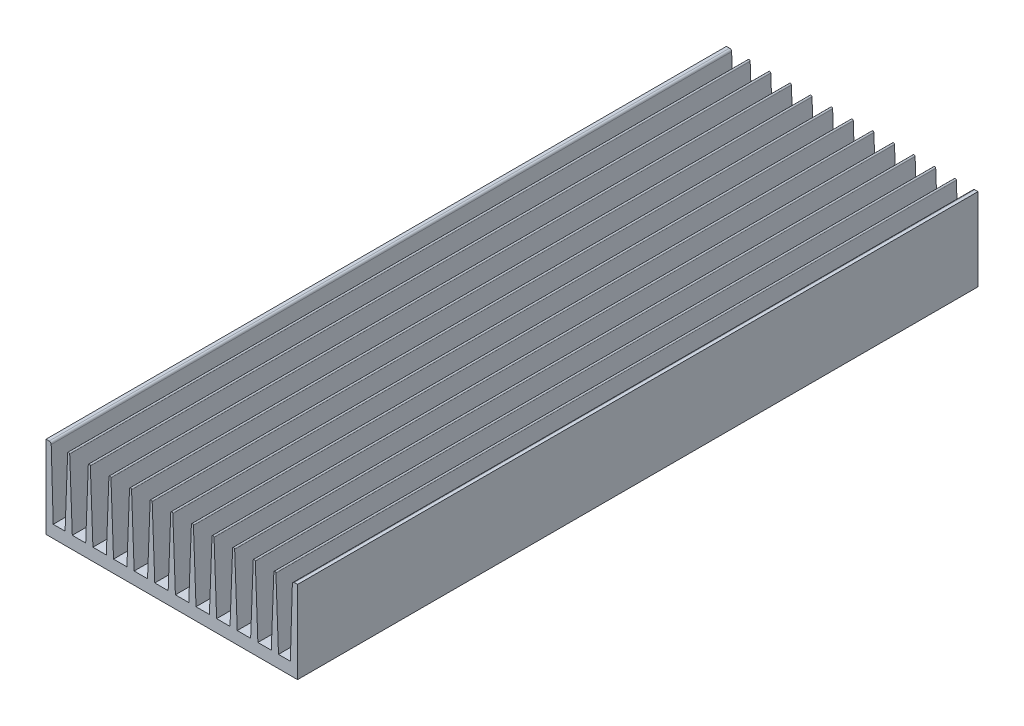
SolidWorks part; units mm, degrees
ref_plane "Спереди" through (0, 0, 0) normal (0, 0, 1) x (1, 0, 0)
ref_plane "Сверху" through (0, 0, 0) normal (0, 1, 0) x (1, 0, 0)
ref_plane "Справа" through (0, 0, 0) normal (1, 0, 0) x (0, 0, -1)
sketch "Эскиз1" plane through (0, 0, 0) normal (0, 0, 1) x (1, 0, 0)
  line L0 (0, 40) -> (1.529, 40)
  line L1 (0, 0) -> (122, 0)
  line L2 (2.5285, 39.0294) -> (3.5, 6)
  line L3 (0, 40) -> (0, 0)
  line L4 (122, 40) -> (122, 0)
  line L5 (61, 63.7127) -> (61, -22.2582) construction
  line L8 (122, 40) -> (120.471, 40)
  line L9 (119.4715, 39.0294) -> (118.5, 6)
  line L10 (3.5, 6) -> (118.5, 6)
  arc A0 (1.529, 40) -> (2.5285, 39.0294) centre (1.529, 39) cw
  arc A2 (120.471, 40) -> (119.4715, 39.0294) centre (120.471, 39) ccw
  point P18 (119.5, 40)
  dimension "D9" = 1
  dimension "D1" = 122
  dimension "D2" = 6
  dimension "D3" = 40
  dimension "D4" = 3.5
  dimension "D7" = 2.5
extrude "Вытянуть1" add sketch "Эскиз1" along normal blind 330
sketch "Эскиз2" plane through (0, 0, 330) normal (0, 0, 1) x (1, 0, 0)
  line L0 (118.5, 6) -> (3.5, 6) construction
  line L1 (10.5, 39.5) -> (9.25, 6)
  line L2 (11, 39.5) -> (11, 22.5548) construction
  line L3 (11.5, 39.5) -> (12.75, 6)
  line L4 (9.25, 6) -> (12.75, 6)
  line L6 (0, 40) -> (0, 0) construction
  arc A0 (10.5, 39.5) -> (11.5, 39.5) centre (11, 39.5) cw
  dimension "D1" = 34
  dimension "D3" = 0.5
  dimension "D2" = 3.5
  dimension "D4" = 11
  dimension "D5" = 1
extrude "Вытянуть3" add sketch "Эскиз2" against normal blind 330
pattern_curve "Кривая1" of "Вытянуть3" along edge at (61, 0, 0) parameters "D1"=11, "D3"=10, "D2"=1, "D4"=50
sketch "Эскиз3" plane through (0, 0, 0) normal (0, -1, 0) x (1, 0, 0)
  line L0 (-14.0506, 321.5) -> (137.5079, 321.5) construction
  line L1 (0, 330) -> (122, 330) construction
  line L2 (0, 330) -> (0, 0) construction
  line L3 (-46.7511, 165) -> (151.4312, 165) construction
  line L4 (0, 0) -> (122, 0) construction
  circle A0 centre (28, 321.5) radius 1.6
  circle A1 centre (94, 321.5) radius 1.6
  circle A2 centre (94, 8.5) radius 1.6
  circle A3 centre (28, 8.5) radius 1.6
  dimension "D2" = 66
  dimension "D4" = 3.2
  dimension "D1" = 8.5
  dimension "D3" = 28
extrude "Вырез-Вытянуть1" cut sketch "Эскиз3" against normal blind 6
cosmetic thread "Условное изображение резьбы1" parameters "D2"=4
cosmetic thread "Условное изображение резьбы2" parameters "D2"=4
cosmetic thread "Условное изображение резьбы3" parameters "D2"=4
cosmetic thread "Условное изображение резьбы4" parameters "D2"=4
